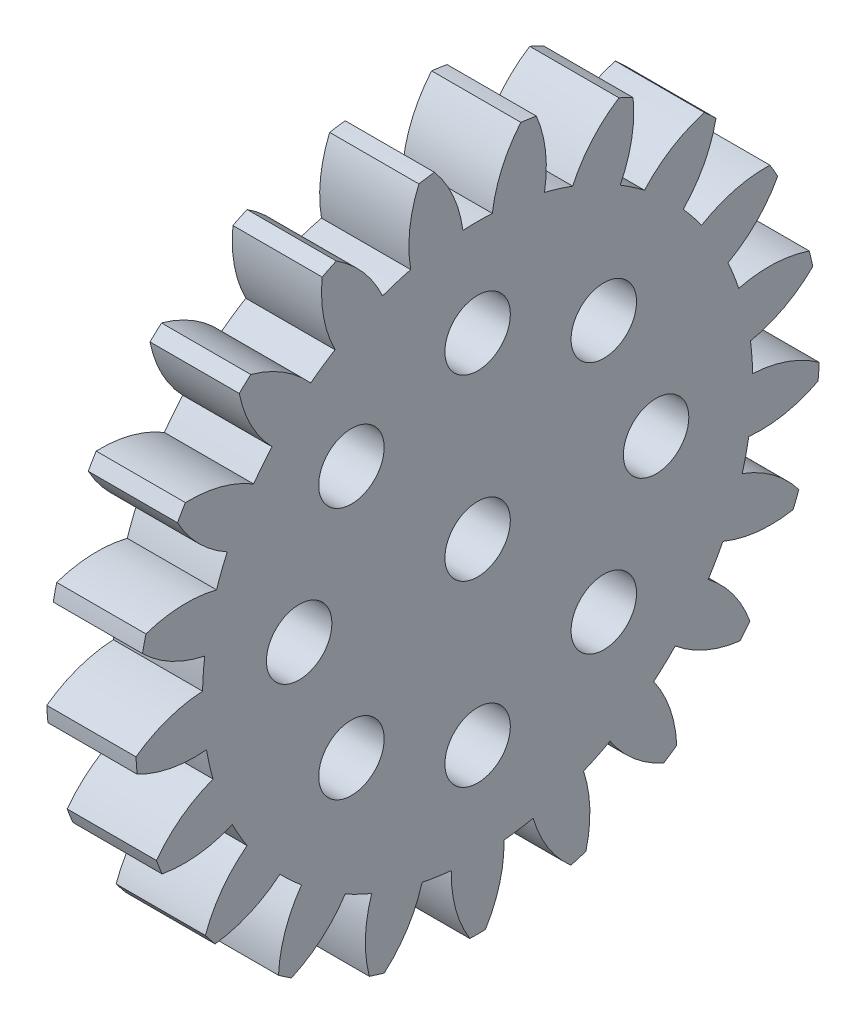
SolidWorks part; units mm, degrees
material "ﾎﾟﾘｵｷｼﾒﾁﾚﾝ(POM)ｱｾﾀｰﾙ共重合体"
ref_plane "Plane1" through (0, 0, 0) normal (0, 0, 1) x (1, 0, 0)
ref_plane "Plane2" through (0, 0, 0) normal (0, 1, 0) x (1, 0, 0)
ref_plane "Plane3" through (0, 0, 0) normal (1, 0, 0) x (0, 0, -1)
other "Configuration Table"
sketch "HoldingSke" plane through (0, 0, 0) normal (0, 1, 0) x (1, 0, 0)
  line L0 (0, 0) -> (0.9336, -0.3584)
  line L1 (-15, 0) -> (100, 0) construction
  line L2 (0, 0) -> (-2.1039, 2.3779)
  line L3 (0, 0) -> (-11.863, 4.5341)
  line L4 (0, 0) -> (8.0624, 3.0949)
  line L5 (0, 0) -> (-46.8476, -17.4728)
  line L6 (0, 0) -> (-2.4869, -1.6779)
  line L7 (-2.1039, 2.3779) -> (8.6586, 51.2059)
  line L8 (-76.2, 54.61) -> (-75.2, 54.61)
  line L9 (-71.009, 38.7566) -> (-53.1078, 45.2721)
  line L10 (-76.2, 71.12) -> (104.1128, 71.12)
  line L11 (0, 0) -> (-3, 0)
  line L12 (-76.2, 101.6) -> (-76.162, 101.6)
  line L13 (24.9733, 27.94) -> (52.9518, 28.4284)
  line L14 (24.9733, 27.94) -> (24.9743, 27.94)
  line L15 (24.9733, 27.94) -> (100.4006, 29.5858)
  line L16 (-63.627, -1) -> (-12.827, -1)
  circle A0 centre (0, 0) radius 4
  circle A1 centre (0, 0) radius 9.249
  circle A2 centre (0, 0) radius 37.5
  circle A3 centre (0, 0) radius 4
  dimension "MHD" = 18.498
  dimension "Hub_dia" = 75
  dimension "Bore" = 8
  dimension "MBD" = 8
  dimension "Num_teeth" = 21
  dimension "Pitch" = 1
  dimension "Overall_len" = 50
  dimension "Show_teeth" = 21
  dimension "Thickness" = 3
  dimension "OAL" = 50.0001
  dimension "T_dim" = 1
  dimension "Ap" = 20
  dimension "H" = 19.05
  dimension "Pitch_radius" = 180.3128
  dimension "Width" = 3
  dimension "Backlash" = 0.038
  dimension "Addendum_fac" = 1
  dimension "Dedendum_fac" = 1.25
  dimension "Clearance_fac" = 0.25
  dimension "Dedendum_add" = 0.001
  dimension "Module" = 1
sketch "BasProSke" plane through (0, 0, 0) normal (0, 1, 0) x (1, 0, 0)
  line L0 (-10, 0) -> (60, 0) construction
  line L1 (0, 0) -> (0, 11.5)
  line L2 (0, 0) -> (3, 0)
  line L3 (3, 0) -> (3, 11.5)
  line L4 (3, 11.5) -> (0, 11.5)
  dimension "Thickness" = 3
  dimension "Diameter" = 23
revolve "Base-Revolve" add sketch "BasProSke" angle 360 about L0
sketch "TooCutSke" plane through (0, 0, 0) normal (1, 0, 0) x (0, 0, -1)
  line L1 (0, 0) -> (0, 107) construction
  line L2 (0, 0) -> (-0.8511, 10.4654) construction
  line L3 (0, 0) -> (-3.1226, 20.7168) construction
  line L4 (-0.8511, 10.4654) -> (-1.5613, 10.3584) construction
  arc A0 (0.4953, 9.2357) -> (-0.4953, 9.2357) centre (0, 0) ccw
  arc A1 (1.4725, 11.431) -> (-1.4725, 11.431) centre (0, 0) ccw
  circle A2 centre (0, 0) radius 10.5 construction
  circle A3 centre (0, 0) radius 9.8668 construction
  arc A4 (-0.4953, 9.2357) -> (-1.4725, 11.431) centre (-4.6605, 8.6967) ccw
  arc A5 (1.4725, 11.431) -> (0.4953, 9.2357) centre (4.6605, 8.6967) ccw
  dimension "Root_dia" = 18.498
  dimension "Overcut_dia" = 23.0508
  dimension "Pitch_dia" = 21
  dimension "Base_dia" = 19.7335
  dimension "Flank_rad" = 4.2
  dimension "Half_ang" = 8.571
  dimension "Half_CT" = 0.7182
extrude "ToothCut" cut sketch "TooCutSke" along normal through all
fillet "Breaks" [suppressed] radius 0.02 tangent propagation no
fillet "RootFillets" [suppressed] radius 0.251
pattern_circular "TeethCuts" count 21 every 17.143 about axis through (-10, 0, 0) along (1, 0, 0) of "ToothCut", "RootFillets", "Breaks"
sketch "HubNeaOneSke" plane through (0, 0, 0) normal (-1, 0, 0) x (0, 0, 1)
  circle A0 centre (0, 0) radius 9.249
  dimension "Diameter" = 18.498
extrude "HubNearOne" [suppressed] add sketch "HubNeaOneSke" along normal blind 47.0001
sketch "HubNeaBotSke" plane through (0, 0, 0) normal (-1, 0, 0) x (0, 0, 1)
  circle A0 centre (0, 0) radius 9.249
  dimension "Diameter" = 18.498
extrude "HubNearBoth" [suppressed] add sketch "HubNeaBotSke" along normal blind 23.5
ref_plane "FarPln" through (3, 0, 0) normal (1, 0, 0) x (0, 0, -1)
sketch "HubFarSke" plane through (3, 0, 0) normal (1, 0, 0) x (0, 0, -1)
  circle A0 centre (0, 0) radius 9.249
  dimension "Diameter" = 18.498
extrude "HubFar" [suppressed] add sketch "HubFarSke" along normal blind 23.5
sketch "BorSke" plane through (0, 0, 0) normal (1, 0, 0) x (0, 0, -1)
  circle A0 centre (0, 0) radius 4
  dimension "Diameter" = 8
extrude "Bore" cut sketch "BorSke" along normal mid plane 100.0001
sketch "KeySke" plane through (0, 0, 0) normal (1, 0, 0) x (0, 0, -1)
  line L0 (-1, 0) -> (-1, 5)
  line L1 (-1, 5) -> (1, 5)
  line L2 (1, 5) -> (1, 0)
  line L3 (0, 0) -> (0, 34) construction
  line L4 (-1, 0) -> (1, 0)
  dimension "Offset" = 5
  dimension "Width" = 2
extrude "Keyway" [suppressed] cut sketch "KeySke" along normal mid plane 100.0001
pattern_circular "Keyway2" [suppressed] count 2 every 90 about axis through (-10, 0, 0) along (1, 0, 0) reverse direction yes
sketch "ｽｹｯﾁ1" plane through (0, 0, 0) normal (-1, 0, 0) x (0, 0, 1)
  circle A0 centre (0, 0) radius 4 construction
  circle A1 centre (0, 0) radius 4
extrude "ﾎﾞｽ - 押し出し1" add sketch "ｽｹｯﾁ1" against normal up to surface (3 mm away) up to face at (3, 0, 4)
sketch "ｽｹｯﾁ2" plane through (3, 0, 0) normal (1, 0, 0) x (0, 0, -1)
  circle A0 centre (0, 0) radius 1.1
  circle A1 centre (0, 0) radius 6 construction
  circle A2 centre (6, 0) radius 1.1
  circle A3 centre (4.2426, -4.2426) radius 1.1
  circle A4 centre (0, -6) radius 1.1
  circle A5 centre (-4.2426, -4.2426) radius 1.1
  circle A6 centre (-6, 0) radius 1.1
  circle A7 centre (-4.2426, 4.2426) radius 1.1
  circle A8 centre (0, 6) radius 1.1
  circle A9 centre (4.2426, 4.2426) radius 1.1
  point P6 (0, 0)
  point P23 (0, 0)
  dimension "D1" = 2.2
  dimension "D2" = 12
  dimension "D3" = 2.2
extrude "ｶｯﾄ - 押し出し1" cut sketch "ｽｹｯﾁ2" against normal through all
equation "' \"Module@HoldingSke\" = 6.35"
equation "' \"Num_teeth@HoldingSke\" = 12"
equation "' \"Ap@HoldingSke\" =  20"
equation "' \"Ap@HoldingSke\" = 20"
equation "' \"Width@HoldingSke\" = 0.5 * 25.4"
equation "' \"Hub_dia@HoldingSke\"= 1 * 25.4"
equation "' \"Hub_dia@HoldingSke\" = 1 * 25.4"
equation "' \"Overall_len@HoldingSke\" = 1.0 * 25.4"
equation "' \"Bore@HoldingSke\" = 0.75 * 25.4"
equation "' \"T_dim@HoldingSke\" = 0.1 * 25.4"
equation "' \"Width@KeySke\" = 0.25 * 25.4"
equation "' \"Show_teeth@HoldingSke\" = 13"
equation "' \"Backlash@HoldingSke\" = 0.009 * 25.4"
equation "' \"Addendum_fac@HoldingSke\" = 1.0"
equation "' \"Dedendum_fac@HoldingSke\" = 1.25"
equation "' \"Dedendum_add@HoldingSke\" = 0.00005 * 25.4"
equation "' \"Clearance_fac@HoldingSke\" = 0.25"
equation "\"Pitch@HoldingSke\" = 1 / \"Module@HoldingSke\""
equation "\"Overcut_dia@TooCutSke\" = (\"Num_teeth@HoldingSke\" + 2 * \"Addendum_fac@HoldingSke\") / \"Pitch@HoldingSke\" + 0.002 * 25.4"
equation "\"Pitch_dia@TooCutSke\" = \"Num_teeth@HoldingSke\" / \"Pitch@HoldingSke\""
equation "\"Base_dia@TooCutSke\" = \"Num_teeth@HoldingSke\" / \"Pitch@HoldingSke\" * cos((\"Ap@HoldingSke\"  * 3.14159265 / 180))"
equation "\"Root_dia@TooCutSke\" = (\"Num_teeth@HoldingSke\" + 2) / \"Pitch@HoldingSke\" - 2 * (\"Addendum_fac@HoldingSke\" + \"Dedendum_fac@HoldingSke\") / \"Pitch@HoldingSke\" - \"Dedendum_add@HoldingSke\" * 2"
equation "\"Half_ang@TooCutSke\" = 180 / \"Num_teeth@HoldingSke\""
equation "\"Half_CT@TooCutSke\" = \"Num_teeth@HoldingSke\" / \"Pitch@HoldingSke\" * sin((3.14159265 / 2 / \"Num_teeth@HoldingSke\")) / 2 - 7 * \"Backlash@HoldingSke\" / 4"
equation "\"Flank_rad@TooCutSke\" = \"Num_teeth@HoldingSke\" / \"Pitch@HoldingSke\" / 5"
equation "\"Radius@RootFillets\" = \"Clearance_fac@HoldingSke\" / \"Pitch@HoldingSke\" + \"Dedendum_add@HoldingSke\""
equation "\"Break_rad@Breaks\" = 0.02 / \"Pitch@HoldingSke\""
equation "\"Thickness@HoldingSke\" = \"Width@HoldingSke\""
equation "\"OAL@HoldingSke\" = \"Thickness@HoldingSke\""
equation "\"MHD@HoldingSke\" = (\"Num_teeth@HoldingSke\" + 2) / \"Pitch@HoldingSke\" - 2 * (\"Addendum_fac@HoldingSke\" + \"Dedendum_fac@HoldingSke\")  / \"Pitch@HoldingSke\" - \"Dedendum_add@HoldingSke\" * 2"
equation "\"MBD@HoldingSke\" = (\"Num_teeth@HoldingSke\" + 2) / \"Pitch@HoldingSke\" - 2 * (\"Addendum_fac@HoldingSke\" + \"Dedendum_fac@HoldingSke\")  / \"Pitch@HoldingSke\" - \"Dedendum_add@HoldingSke\" * 2 - 0.002 * 25.4"
equation "\"MHD@HoldingSke\" = ((sgn( \"MHD@HoldingSke\" - \"Hub_dia@HoldingSke\" )-1)*( \"MHD@HoldingSke\" - \"Hub_dia@HoldingSke\" ))/-2+ \"Hub_dia@HoldingSke\""
equation "\"MBD@HoldingSke\" = ((sgn( \"MBD@HoldingSke\" - \"Bore@HoldingSke\" )-1)*( \"MBD@HoldingSke\" - \"Bore@HoldingSke\" ))/-2+ \"Bore@HoldingSke\""
equation "\"OAL@HoldingSke\" = ((sgn( \"OAL@HoldingSke\" - \"Overall_len@HoldingSke\" )+1)*( \"OAL@HoldingSke\" - \"Overall_len@HoldingSke\" ))/2 + \"Overall_len@HoldingSke\" + 0.000002 * 25.4"
equation "\"Num_teeth@TeethCuts\" = int( \"Show_teeth@HoldingSke\" ) + 1"
equation "\"Num_teeth@TeethCuts\" = ((sgn( \"Num_teeth@TeethCuts\" - \"Num_teeth@HoldingSke\" )-1)*( \"Num_teeth@TeethCuts\" - \"Num_teeth@HoldingSke\" ))/-2+ \"Num_teeth@HoldingSke\""
equation "\"Num_teeth@TeethCuts\" = ((sgn( \"Num_teeth@TeethCuts\" - 2.0)+1)*( \"Num_teeth@TeethCuts\" - 2.0))/2 +2.0"
equation "\"Angle@TeethCuts\" = 360.0 / \"Num_teeth@HoldingSke\""
equation "\"Diameter@BasProSke\" = (\"Num_teeth@HoldingSke\" + 2 * \"Addendum_fac@HoldingSke\") / \"Pitch@HoldingSke\""
equation "\"Thickness@BasProSke\"  = \"Thickness@HoldingSke\""
equation "' \"Fillet_rad@BasProSke\" =  \"Thickness@HoldingSke\" * 0.05"
equation "' \"Fillet_rad@BasProSke\" = \"Thickness@HoldingSke\" * 0.05"
equation "\"MHD@HoldingSke\" = ((sgn( \"MHD@HoldingSke\" - \"Root_dia@TooCutSke\" )-1)*( \"MHD@HoldingSke\" - \"Root_dia@TooCutSke\" ))/-2+ \"Root_dia@TooCutSke\""
equation "\"Diameter@HubNeaOneSke\" = \"MHD@HoldingSke\""
equation "\"Length@HubNearOne\" = \"OAL@HoldingSke\" - \"Thickness@BasProSke\""
equation "\"Diameter@HubNeaBotSke\" = \"MHD@HoldingSke\""
equation "\"Length@HubNearBoth\" = ( \"OAL@HoldingSke\" - \"Thickness@BasProSke\" ) / 2.0"
equation "\"Thickness@FarPln\" = \"Thickness@BasProSke\""
equation "\"Diameter@HubFarSke\" = \"MHD@HoldingSke\""
equation "\"Length@HubFar\" = ( \"OAL@HoldingSke\" - \"Thickness@BasProSke\" ) / 2.0"
equation "\"Diameter@BorSke\" = \"MBD@HoldingSke\""
equation "\"D1@Bore\" = \"OAL@HoldingSke\" * 2.0"
equation "\"D1@Keyway\" = \"OAL@HoldingSke\" * 2.0"
equation "\"Offset@KeySke\" = \"T_dim@HoldingSke\" + \"MBD@HoldingSke\" / 2.0"
